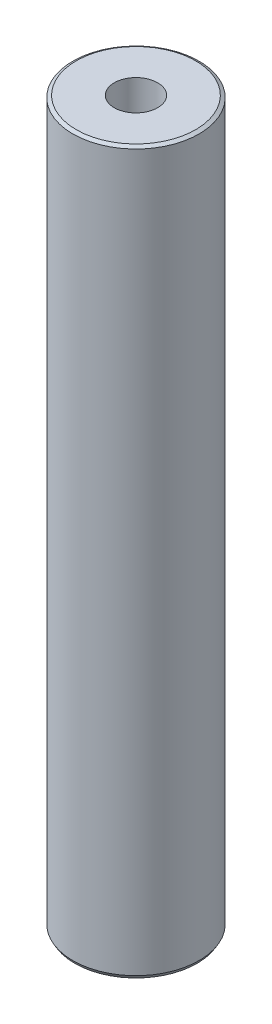
SolidWorks part; units mm, degrees
ref_plane "Front Plane" through (0, 0, 0) normal (0, 0, 1) x (1, 0, 0)
ref_plane "Top Plane" through (0, 0, 0) normal (0, 1, 0) x (1, 0, 0)
ref_plane "Right Plane" through (0, 0, 0) normal (1, 0, 0) x (0, 0, -1)
sketch "Sketch1" plane through (0, 0, 0) normal (0, 1, 0) x (1, 0, 0)
  circle A0 centre (0, 0) radius 52.5
  dimension "SHAFT_OD" = 105
extrude "Boss-Extrude1" add sketch "Sketch1" along normal blind 600
sketch "Sketch2" plane through (0, 0, 0) normal (0, 1, 0) x (1, 0, 0)
  circle A0 centre (0, 0) radius 18.0358
  dimension "BORE_D" = 36.0717
extrude "Cut-Extrude1" cut sketch "Sketch2" along normal through all
chamfer "Chamfer1" distance 1.6417 angle 60 2 edges at (0, 600, 52.5) (0, 0, 52.5) first distance on face at (0, 600, 52.5) first distance on face at (0, 0, 18.0358)
